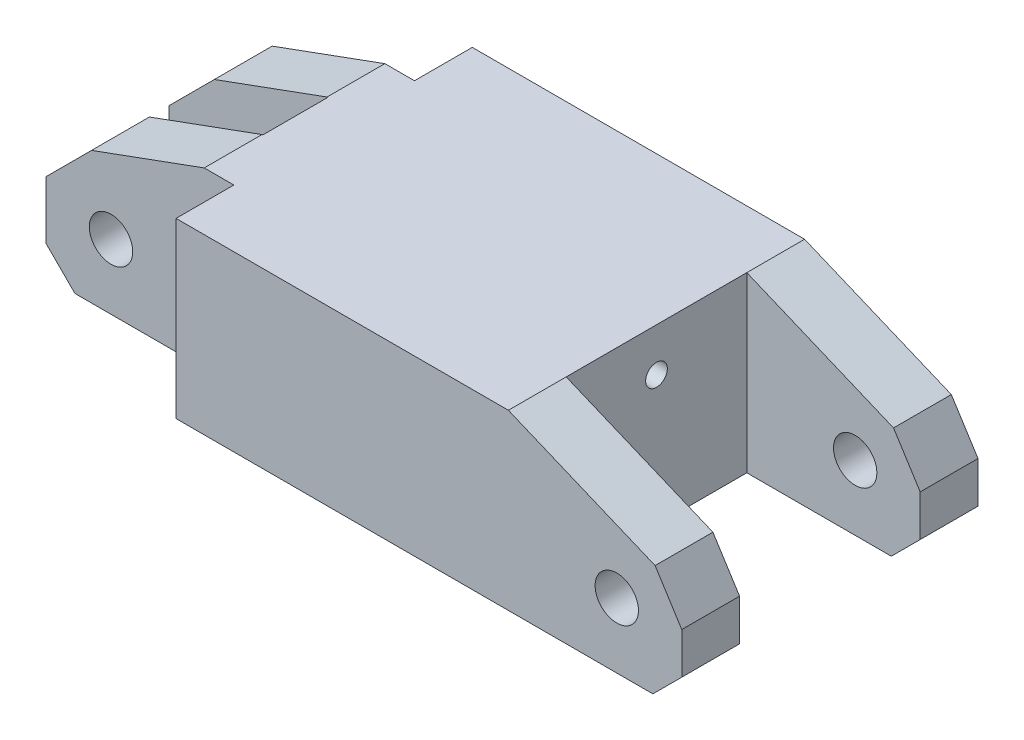
SolidWorks part; units mm, degrees
ref_plane "Спереди" through (0, 0, 0) normal (0, 0, 1) x (1, 0, 0)
ref_plane "Сверху" through (0, 0, 0) normal (0, 1, 0) x (1, 0, 0)
ref_plane "Справа" through (0, 0, 0) normal (1, 0, 0) x (0, 0, -1)
sketch "Эскиз2" plane through (0, 0, 0) normal (1, 0, 0) x (0, 0, -1)
  line L1 (-10.25, 6) -> (10.25, 6)
  line L2 (-10.25, 6) -> (-10.25, -6)
  line L3 (-10.25, -6) -> (10.25, -6)
  line L4 (10.25, 6) -> (10.25, -6)
  line L5 (-10.25, 6) -> (10.25, -6) construction
  line L6 (-10.25, -6) -> (10.25, 6) construction
  point P0 (0, 0)
extrude "Вытянуть1" add sketch "Эскиз2" along normal blind 48
sketch "Эскиз3" plane through (0, 6, 0) normal (0, 1, 0) x (1, 0, 0)
  line L0 (0, 0) -> (-9.2006, 0) construction
  line L1 (0, 10.25) -> (0, -10.25) construction
  line L2 (-11, 2.25) -> (11, 2.25)
  line L3 (-11, 2.25) -> (-11, -2.25)
  line L4 (-11, -2.25) -> (11, -2.25)
  line L5 (11, 2.25) -> (11, -2.25)
  line L6 (-11, 2.25) -> (11, -2.25) construction
  line L7 (-11, -2.25) -> (11, 2.25) construction
  point P1 (0, 0)
  dimension "D1" = 11
extrude "Вырез-Вытянуть1" cut sketch "Эскиз3" against normal through all
sketch "Эскиз5" plane through (0, 6, 0) normal (0, 1, 0) x (1, 0, 0)
  line L0 (40, 0) -> (51.6105, 0) construction
  line L1 (48, 10.25) -> (0, 10.25) construction
  line L2 (48, 10.25) -> (48, -10.25) construction
  line L3 (36, 6.25) -> (48, 6.25)
  line L4 (36, 6.25) -> (36, -6.25)
  line L5 (36, -6.25) -> (48, -6.25)
  line L6 (48, 6.25) -> (48, -6.25)
  line L7 (36, 6.25) -> (48, -6.25) construction
  line L8 (36, -6.25) -> (48, 6.25) construction
  point P1 (42, 0)
  dimension "D1" = 12
  dimension "D2" = 4
extrude "Вырез-Вытянуть2" cut sketch "Эскиз5" against normal through all
sketch "Эскиз7" plane through (36, 0, 0) normal (1, 0, 0) x (0, 0, -1)
  line L0 (0, 6) -> (0, 3.9395) construction
  line L1 (6.25, 6) -> (-6.25, 6) construction
  circle A0 centre (0, 3) radius 0.75
  dimension "D1" = 3
extrude "Вытянуть3" cut sketch "Эскиз7" against normal through all
sketch "Эскиз10" plane through (0, 6, 0) normal (0, 1, 0) x (1, 0, 0)
  line L0 (5.6157, 0) -> (-3.5713, 0) construction
  line L1 (0, 10.25) -> (0, 2.25) construction
  line L2 (11, 2.25) -> (0, 2.25) construction
  line L3 (-6.1065, 15.2007) -> (13, 15.2007)
  line L4 (-6.1065, 15.2007) -> (-6.1065, 6.25)
  line L5 (-6.1065, 6.25) -> (13, 6.25)
  line L6 (13, 15.2007) -> (13, 6.25)
  line L7 (-6.1065, -15.2007) -> (13, -15.2007)
  line L8 (-6.1065, -15.2007) -> (-6.1065, -6.25)
  line L9 (-6.1065, -6.25) -> (13, -6.25)
  line L10 (13, -15.2007) -> (13, -6.25)
  dimension "D1" = 4
  dimension "D2" = 13
extrude "Вырез-Вытянуть3" cut sketch "Эскиз10" against normal through all
sketch "Эскиз11" plane through (0, 0, 6.25) normal (0, 0, 1) x (1, 0, 0)
  line L0 (0, -6) -> (0, 6) construction
  line L2 (13, -6) -> (0, -6) construction
  circle A0 centre (4.5, -1.5) radius 1.5
  dimension "D1" = 4.5
  dimension "D2" = 4.5
extrude "Вытянуть6" cut sketch "Эскиз11" against normal through all
sketch "Эскиз9" plane through (0, 0, 10.25) normal (0, 0, 1) x (1, 0, 0)
  line L0 (48, 6) -> (48, -6) construction
  line L2 (48, -6) -> (13, -6) construction
  circle A0 centre (43.5, -1.5) radius 1.5
  dimension "D1" = 4.5
  dimension "D2" = 4.5
extrude "Вытянуть5" cut sketch "Эскиз9" against normal through all
sketch "Эскиз12" plane through (11, 0, 0) normal (-1, 0, 0) x (0, 0, 1)
  circle A0 centre (-1.7914, -3.4073) radius 0.75
extrude "Вырез-Вытянуть4" cut sketch "Эскиз12" against normal blind 12
sketch "Эскиз13" plane through (0, 0, 10.25) normal (0, 0, 1) x (1, 0, 0)
  line L0 (10.95, 6) -> (0, 6)
  line L1 (48, 6) -> (13, 6) construction
  line L2 (0, -6) -> (0, 6) construction
  line L3 (0, 6) -> (0, 2)
  line L4 (0, 2) -> (10.95, 6)
  line L5 (48, 6) -> (48, -6) construction
  line L6 (48, 6) -> (48, 1)
  line L7 (13, 6) -> (0, 6) construction
  line L8 (48, 1) -> (36, 6)
  line L9 (36, 6) -> (48, 6)
  dimension "D2" = 4
  dimension "D1" = 10.95
  dimension "D3" = 12
extrude "Вытянуть7" cut sketch "Эскиз13" against normal through all
chamfer "Фаска5" distance 2 angle 45 6 edges at (0, -6, 4.25) (0, -6, -4.25) (0, 2, 4.25) (0, 2, -4.25) (48, -6, -8.25) (48, -6, 8.25) first distance on face at (0, -2, 4.25) first distance on face at (0, -2, -4.25) first distance on face at (48, -2.5, -8.25) first distance on face at (48, -2.5, 8.25)
chamfer "Фаска6" distance 2 angle 35 2 edges at (48, 1, -8.25) (48, 1, 8.25) first distance on face at (42, 3.5, -8.25) first distance on face at (42, 3.5, 8.25)
sketch "Эскиз14" plane through (36, 0, 0) normal (1, 0, 0) x (0, 0, -1)
  circle A0 centre (-1.7679, -3.8676) radius 0.75
extrude "Вырез-Вытянуть5" cut sketch "Эскиз14" against normal blind 5
sketch "Эскиз15" plane through (0, -6, 0) normal (0, -1, 0) x (1, 0, 0)
  line L0 (13, 10.25) -> (13, 6.25) construction
  line L1 (18, 6.25) -> (31, 6.25)
  line L2 (16, 4.25) -> (16, -4.25)
  line L3 (18, -6.25) -> (31, -6.25)
  line L4 (33, 4.25) -> (33, -4.25)
  line L5 (36, -6.25) -> (36, 6.25) construction
  line L6 (46, 10.25) -> (13, 10.25) construction
  line L7 (46, -10.25) -> (13, -10.25) construction
  arc A0 (18, 6.25) -> (16, 4.25) centre (18, 4.25) ccw
  arc A1 (33, 4.25) -> (31, 6.25) centre (31, 4.25) ccw
  arc A2 (31, -6.25) -> (33, -4.25) centre (31, -4.25) ccw
  arc A3 (16, -4.25) -> (18, -6.25) centre (18, -4.25) ccw
  dimension "D5" = 2
  dimension "D1" = 3
  dimension "D2" = 3
  dimension "D3" = 4
  dimension "D4" = 4
extrude "Вытянуть8" cut sketch "Эскиз15" against normal blind 10
